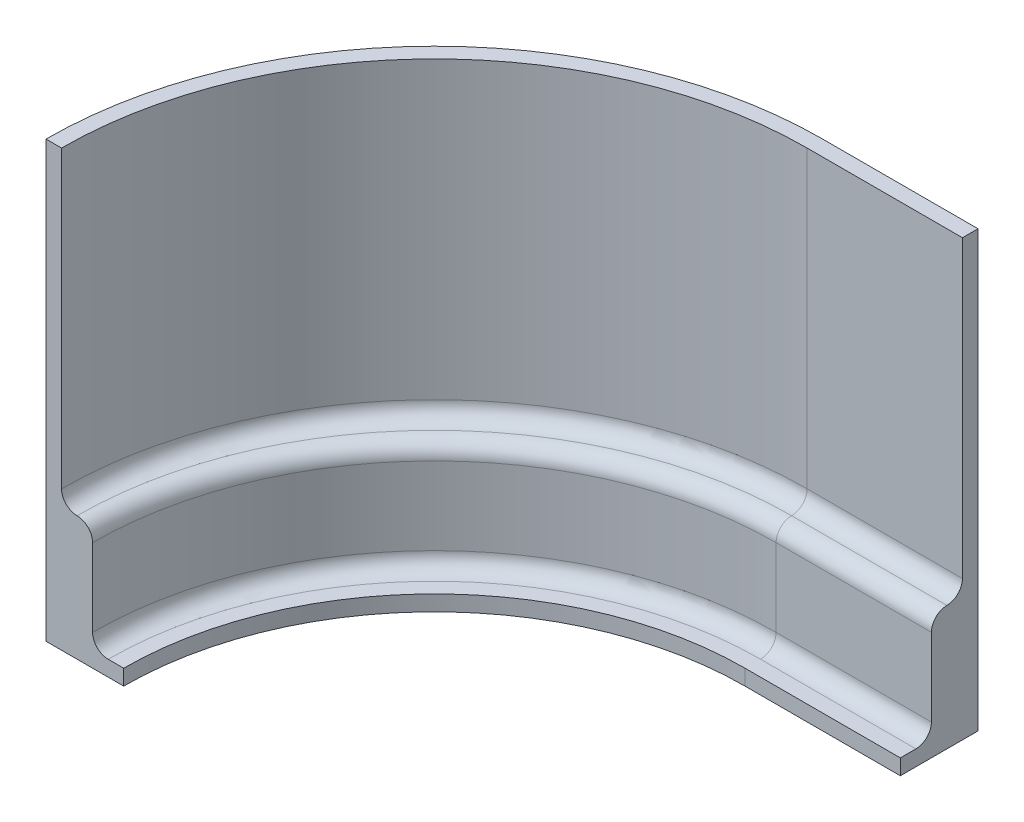
SolidWorks part; units mm, degrees
material "AISI 4340 Steel, annealed"
ref_plane "Front Plane" through (0, 0, 0) normal (0, 0, 1) x (1, 0, 0)
ref_plane "Top Plane" through (0, 0, 0) normal (0, 1, 0) x (1, 0, 0)
ref_plane "Right Plane" through (0, 0, 0) normal (1, 0, 0) x (0, 0, -1)
sketch "Sketch1" plane through (0, 0, 0) normal (0, 1, 0) x (1, 0, 0)
  line L0 (0, 0) -> (-25, 0)
  line L1 (100, 125) -> (150, 125)
  line L2 (150, 125) -> (150, 100)
  line L3 (150, 100) -> (100, 100)
  arc A0 (0, 0) -> (100, 100) centre (100, 0) cw
  arc A1 (-25, 0) -> (100, 125) centre (100, 0) cw
  dimension "D1" = 100
  dimension "D2" = 25
  dimension "D3" = 50
extrude "Bottom level" add sketch "Sketch1" along normal blind 5
sketch "Sketch2" plane through (0, 5, 0) normal (0, 1, 0) x (1, 0, 0)
  line L0 (150, 125) -> (100, 125) construction
  line L1 (150, 125) -> (100, 125)
  line L2 (-25, 0) -> (0, 0) construction
  line L3 (-25, 0) -> (-10, 0)
  line L4 (150, 125) -> (150, 110)
  line L5 (150, 100) -> (150, 125) construction
  line L6 (150, 110) -> (100, 110)
  arc A0 (100, 125) -> (-25, 0) centre (100, 0) ccw construction
  arc A1 (100, 125) -> (-25, 0) centre (100, 0) ccw
  arc A2 (-10, 0) -> (100, 110) centre (100, 0) cw
  dimension "D1" = 15
extrude "Mid level" add sketch "Sketch2" along normal blind 35
sketch "Sketch3" plane through (0, 40, 0) normal (0, 1, 0) x (1, 0, 0)
  line L0 (150, 125) -> (100, 125) construction
  line L1 (150, 125) -> (100, 125)
  line L2 (150, 120) -> (100, 120)
  line L3 (-25, 0) -> (-20, 0)
  line L4 (150, 125) -> (150, 120)
  arc A0 (100, 125) -> (-25, 0) centre (100, 0) ccw construction
  arc A1 (100, 125) -> (-25, 0) centre (100, 0) ccw
  arc A2 (100, 120) -> (-20, 0) centre (100, 0) ccw
  dimension "D1" = 5
extrude "Guard rail" add sketch "Sketch3" along normal blind 100
fillet "Rounding" radius 5 6 edges at (125, 5, -110) (125, 40, -120) (125, 40, -110) (22.2183, 5, -77.7817) (15.1472, 40, -84.8528) (22.2183, 40, -77.7817)
